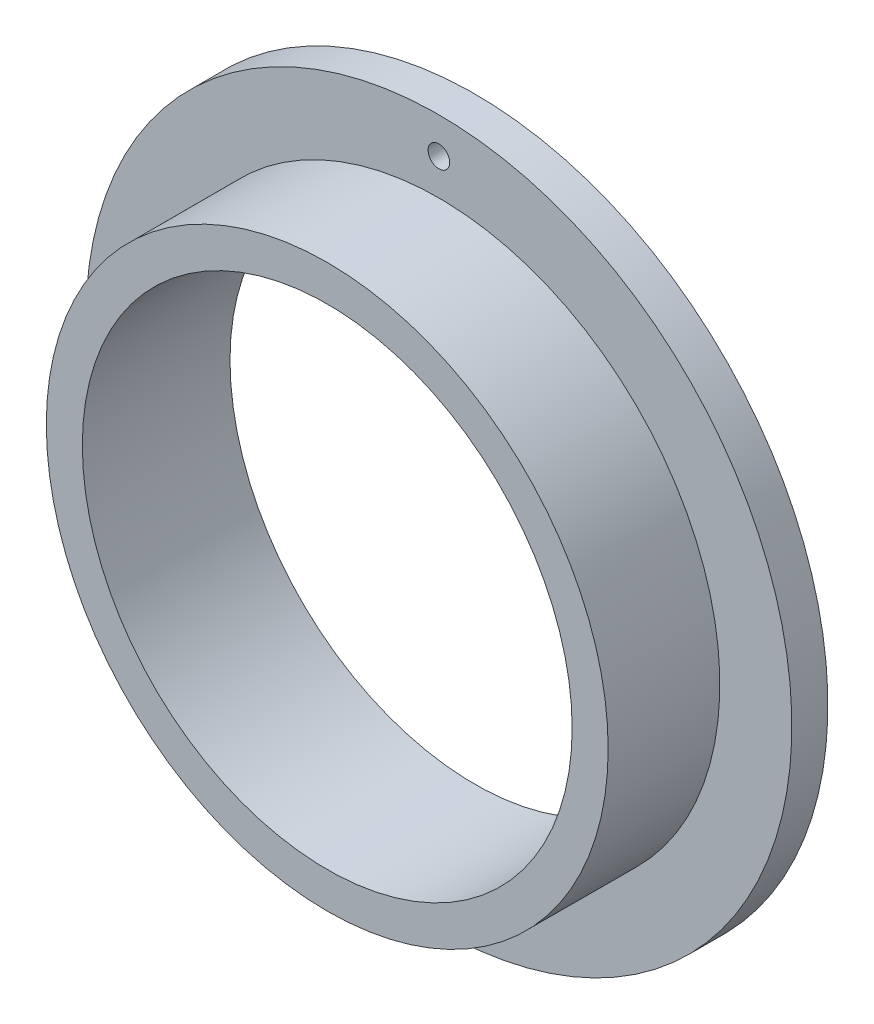
SolidWorks part; units mm, degrees
ref_plane "Plan de face" through (0, 0, 0) normal (0, 0, 1) x (1, 0, 0)
ref_plane "Plan de dessus" through (0, 0, 0) normal (0, 1, 0) x (1, 0, 0)
ref_plane "Plan de droite" through (0, 0, 0) normal (1, 0, 0) x (0, 0, -1)
sketch "Esquisse1" plane through (0, 0, 0) normal (0, 0, 1) x (1, 0, 0)
  circle A0 centre (0, 0) radius 39
  circle A1 centre (0, 0) radius 34
  dimension "D1" = 78
  dimension "D2" = 5
extrude "Boss.-Extru.1" add sketch "Esquisse1" along normal blind 15.5
sketch "Esquisse2" plane through (0, 0, 0) normal (0, 0, -1) x (-1, 0, 0)
  circle A0 centre (0, 0) radius 49
  circle A1 centre (0, 0) radius 39 construction
  dimension "D1" = 10
extrude "Boss.-Extru.2" add sketch "Esquisse2" along normal blind 5
sketch "Esquisse3" plane through (0, 0, -5) normal (0, 0, -1) x (-1, 0, 0)
  circle A0 centre (0, 0) radius 34
  circle A1 centre (0, 0) radius 34 construction
extrude "Enlèv. mat.-Extru.1" cut sketch "Esquisse3" against normal through all
sketch "Esquisse4" plane through (0, 0, -5) normal (0, 0, -1) x (-1, 0, 0)
  line L0 (0, -39) -> (0, -49) construction
  line L1 (0, 49) -> (0, 39) construction
  circle A0 centre (0, 0) radius 49 construction
  circle A1 centre (0, 44) radius 1.5
  circle A2 centre (0, -44) radius 1.5
  circle A4 centre (0, 0) radius 39 construction
  dimension "D1" = 3
extrude "Enlèv. mat.-Extru.2" cut sketch "Esquisse4" against normal through all
